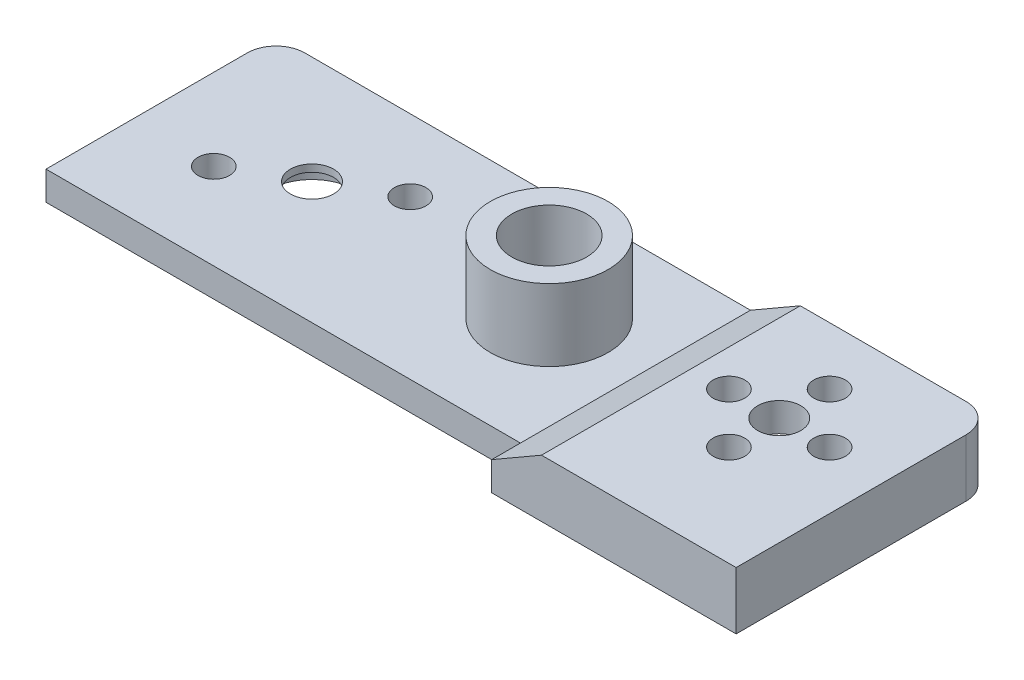
SolidWorks part; units mm, degrees
note: The reader was unsure of these and kept them because the rebuilt part matched: shared geometry of "草图1<7>", "草图1<8>".
ref_plane "前视基准面" through (0, 0, 0) normal (0, 0, 1) x (1, 0, 0)
ref_plane "上视基准面" through (0, 0, 0) normal (0, 1, 0) x (1, 0, 0)
ref_plane "右视基准面" through (0, 0, 0) normal (1, 0, 0) x (0, 0, -1)
other "Configuration Table"
sketch "草图1" plane through (0, 0, 0) normal (0, 1, 0) x (1, 0, 0)
  line L0 (-25, 7.5) -> (25, 7.5)
  line L1 (25, 7.5) -> (25, -7.5)
  line L2 (25, -7.5) -> (-25, -7.5)
  line L3 (-25, -7.5) -> (-25, 7.5)
  line L4 (-25, 0) -> (25, 0) construction
  line L5 (-19.3301, -2.5) -> (-10.6699, 2.5) construction
  line L6 (-19.8083, -5.95) -> (-10.1917, -5.95) construction
  line L7 (-19.8083, 5.95) -> (-10.1917, 5.95) construction
  line L8 (-15, 0) -> (-15, 4.4384) construction
  line L10 (25, 7.5) -> (8, 7.5)
  line L11 (25, 7.5) -> (25, -7.5)
  line L12 (25, -7.5) -> (8, -7.5)
  line L13 (8, 7.5) -> (8, -7.5)
  circle A0 centre (-15, 0) radius 1.5
  circle A1 centre (-10.6699, 2.5) radius 1.1
  circle A3 centre (-19.3301, -2.5) radius 1.1
  arc A4 (-19.8083, 5.95) -> (-19.8083, -5.95) centre (-15, 0) ccw construction
  circle A5 centre (1.5, 0) radius 2.6
  arc A6 (-10.1917, -5.95) -> (-10.1917, 5.95) centre (-15, 0) ccw construction
  circle A7 centre (17.5, 0) radius 1.5
  circle A8 centre (17.5, 0) radius 3.5 construction
  circle A9 centre (21, 0) radius 1.1
  circle A10 centre (17.5, -3.5) radius 1.1
  circle A11 centre (14, 0) radius 1.1
  circle A12 centre (17.5, 3.5) radius 1.1
  circle A13 centre (-10.6699, -2.5) radius 1.1
  circle A14 centre (-19.3301, 2.5) radius 1.1
  circle A20 centre (17.5, 0) radius 6
  circle A21 centre (1.5, 0) radius 7
  point P5 (0, 7.5)
  point P7 (-25, 0)
  dimension "D3" = 3
  dimension "D6" = 2.2
  dimension "D9" = 15.3
  dimension "D12" = 5.2
  dimension "D14" = 3
  dimension "D15" = 7
  dimension "D16" = 2.2
  dimension "D22" = 12
  dimension "D23" = 14
  dimension "D1" = 50
  dimension "D2" = 15
  dimension "D4" = 40
  dimension "D7" = 30
  dimension "D8" = 10
  dimension "D10" = 11.9
  dimension "D11" = 16.5
  dimension "D13" = 16
  dimension "D21" = 17
  dimension "D5" = 2
  dimension "D17" = 4
extrude "凸台-拉伸1" add sketch "草图1" along normal blind 2
sketch "草图3" plane through (0, 0, 0) normal (0, -1, 0) x (1, 0, 0)
  circle A0 centre (-15, 0) radius 3
  dimension "D1" = 6
extrude "切除-拉伸1" cut sketch "草图3" against normal blind 1.5
extrude "凸台-拉伸4" add sketch "草图1<7>" along normal blind 4 contours L11 L10 L13 L12 | A12 | A9 | A10 | A7 | A11
sketch "草图1<7>" plane through (0, 0, 0) normal (0, 1, 0) x (1, 0, 0) same geometry as "草图1"
extrude "切除-拉伸4" cut sketch "草图1<8>" along normal blind 2 contours A20 A7 A9 A10 A11 A12
sketch "草图1<8>" plane through (0, 0, 0) normal (0, 1, 0) x (1, 0, 0) same geometry as "草图1"
sketch "草图6" plane through (0, 0, -7.5) normal (0, 0, -1) x (-1, 0, 0)
  line L0 (-8, 2) -> (-11.4641, 4)
  line L1 (-25, 4) -> (-8, 4) construction
  line L2 (-11.4641, 4) -> (-8, 4)
  line L3 (-8, 4) -> (-8, 2) construction
  line L4 (-8, 4) -> (-8, 2)
  dimension "D1" = 30
extrude "切除-拉伸5" cut sketch "草图6" against normal up to surface (15 mm away) up to face at (2.6667, 2, 7.5)
sketch "草图8" plane through (0, 0, 0) normal (0, -1, 0) x (1, 0, 0)
  circle A0 centre (1.5, 0) radius 2.6
  circle A1 centre (1.5, 0) radius 5.5
  circle A2 centre (1.5, 0) radius 2.6 construction
  dimension "D1" = 11
extrude "凸台-拉伸11" add sketch "草图8" along normal blind 2
sketch "草图10" plane through (0, -2, 0) normal (0, -1, 0) x (1, 0, 0)
  line L0 (1.5, 0) -> (1.5, 4.0685) construction
  line L1 (8, 0) -> (4.0288, 0) construction
  line L2 (1.5, 3.1754) -> (-1.25, 1.5877)
  line L3 (-1.25, 1.5877) -> (-1.25, -1.5877)
  line L4 (1.5, 3.1754) -> (4.25, 1.5877)
  line L5 (4.25, 1.5877) -> (4.25, -1.5877)
  line L6 (1.5, -3.1754) -> (4.25, -1.5877)
  line L7 (1.5, -3.1754) -> (-1.25, -1.5877)
  circle A2 centre (1.5, 0) radius 2.6 construction
  point P1 (1.5, 2.0343)
  point P11 (1.5, 0)
  point P18 (4.25, 0)
  point P20 (-1.25, 0)
  dimension "D1" = 120
  dimension "D2" = 5.5
  dimension "D3" = 5.5
extrude "切除-拉伸6" cut sketch "草图10" against normal blind 3.5
sketch "草图11" plane through (0, -2, 0) normal (0, -1, 0) x (1, 0, 0)
  line L0 (-3.399, 2.5) -> (6.399, 2.5)
  line L2 (25, 7.5) -> (-25, 7.5) construction
  circle A0 centre (1.5, 0) radius 5.5 construction
  arc A1 (-3.399, 2.5) -> (6.399, 2.5) centre (1.5, 0) cw
  dimension "D1" = 5
extrude "切除-拉伸7" cut sketch "草图11" against normal up to surface (2 mm away) up to face at (-15, 0, -3)
fillet "圆角1" radius 2 2 edges at (-25, 1, -7.5) (25, 2, -7.5)
sketch "草图13" plane through (0, 0, 7.5) normal (0, 0, 1) x (1, 0, 0)
  line L6 (11.4641, 4) -> (8, 2)
  line L7 (8, 2) -> (-25, 2)
  line L8 (-25, 2) -> (-25, 0)
  line L9 (-25, 0) -> (25, 0)
  line L10 (25, 0) -> (25, 4)
  line L11 (25, 4) -> (11.4641, 4)
  line L12 (11.4641, 4) -> (8, 2)
  line L13 (8, 2) -> (-25, 2)
  line L14 (-25, 2) -> (-25, 0)
  line L15 (-25, 0) -> (25, 0)
  line L16 (25, 0) -> (25, 4)
  line L17 (25, 4) -> (11.4641, 4)
  dimension "D1" = 0
extrude "凸台-拉伸15" add sketch "草图13" along normal blind 1
sketch "草图14" plane through (0, 0, 8.5) normal (0, 0, 1) x (1, 0, 0)
  line L0 (8, 0) -> (8, 2)
  line L2 (8, 2) -> (-25, 2) construction
  line L11 (25, 4) -> (11.4641, 4)
  line L13 (11.4641, 4) -> (8, 2)
  line L21 (8, 2) -> (-25, 2)
  line L22 (-25, 2) -> (-25, 0)
  line L23 (-25, 0) -> (25, 0)
  line L24 (25, 0) -> (25, 4)
  line L25 (25, 4) -> (11.4641, 4)
  line L26 (11.4641, 4) -> (8, 2)
  line L29 (8, 0) -> (25, 0)
  line L30 (25, 0) -> (25, 4)
  dimension "D1" = 0
extrude "凸台-拉伸16" add sketch "草图14" along normal blind 2
sketch "草图16" plane through (0, 2, 0) normal (0, 1, 0) x (1, 0, 0)
  circle A0 centre (1.5, 0) radius 2.6 construction
  circle A1 centre (1.5, 0) radius 2.6
  circle A2 centre (1.5, 0) radius 4.1
  dimension "D1" = 1.5
extrude "凸台-拉伸18" add sketch "草图16" along normal blind 5
fillet "圆角3" radius 0.5 9 edges at (-0.4599, -2, 2.0439) (-1.25, -2, 0) (0.125, -2, -2.3816) (2.875, -2, -2.3816) (4.25, -2, 0) (3.4599, -2, 2.0439) (4.5344, -2, 2.5) (1.5, -2, -5.5) (-1.5344, -2, 2.5)
